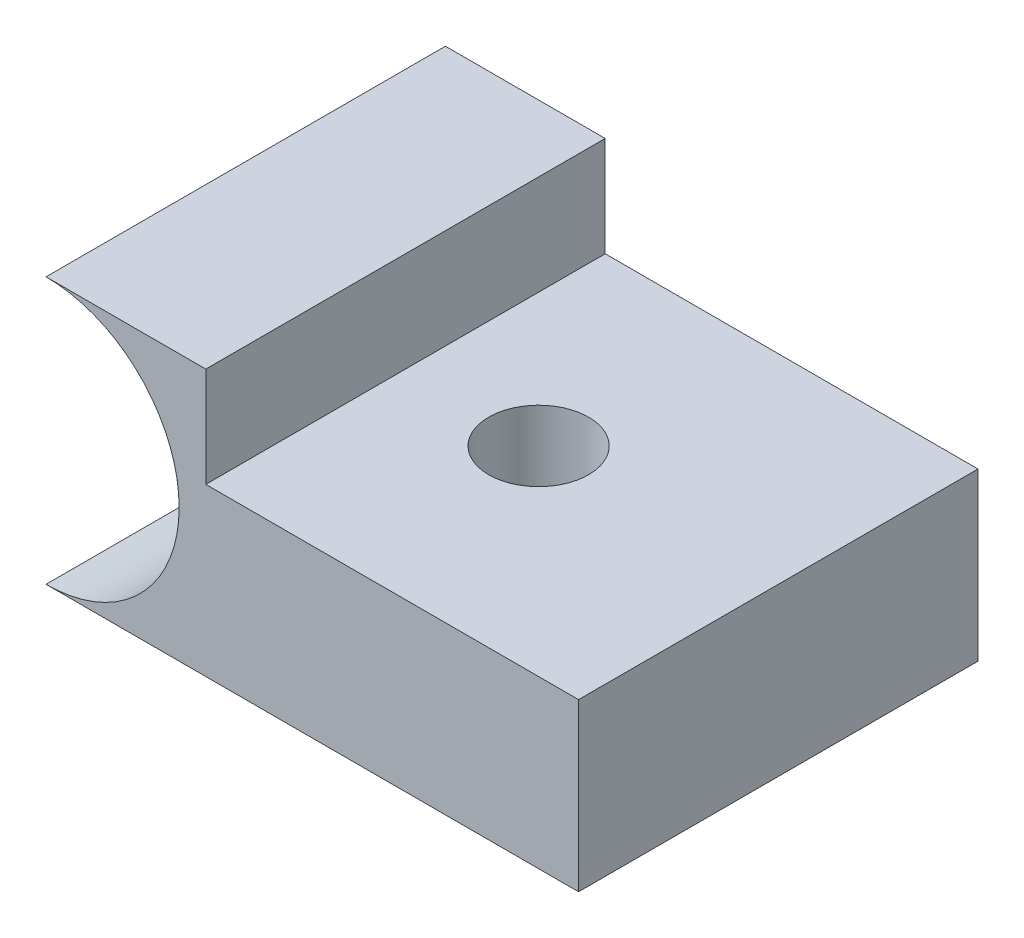
SolidWorks part; units mm, degrees
material "AISI Type A2 Tool Steel"
ref_plane "Front Plane" through (0, 0, 0) normal (0, 0, 1) x (1, 0, 0)
ref_plane "Top Plane" through (0, 0, 0) normal (0, 1, 0) x (1, 0, 0)
ref_plane "Right Plane" through (0, 0, 0) normal (1, 0, 0) x (0, 0, -1)
sketch "Sketch1" plane through (0, 0, 0) normal (0, 0, 1) x (1, 0, 0)
  line L1 (0, 0) -> (50.8, 0)
  line L3 (0, 25.4) -> (15.24, 25.4)
  line L4 (50.8, 0) -> (50.8, 15.875)
  line L6 (15.24, 25.4) -> (15.24, 15.875)
  line L7 (15.24, 15.875) -> (50.8, 15.875)
  arc A1 (0, 0) -> (0, 25.4) centre (0, 12.7) ccw
  dimension "D2" = 25.4
  dimension "D1" = 50.8
  dimension "D3" = 9.525
  dimension "D4" = 15.24
extrude "Boss-Extrude1" add sketch "Sketch1" along normal blind 38.1
sketch "Sketch2" plane through (0, 15.875, 0) normal (0, 1, 0) x (1, 0, 0)
  line L0 (0, -38.1) -> (0, 0) construction
  point P0 (27.94, -19.05)
  point P5 (0, -19.05)
  dimension "D1" = 27.94
hole_wizard "3/8 (0.375) Diameter Hole1" positions "Sketch2" profile "Sketch4" hole size "3/8" standard "ANSI Inch" end condition through all
sketch "Sketch4" plane through (27.94, 15.875, 19.05) normal (1, 0, 0) x (0, 0, 1)
  line L0 (0, 0) -> (0, 15.875)
  line L1 (0, 15.875) -> (4.7625, 15.875)
  line L2 (4.7625, 15.875) -> (4.7625, 0)
  line L5 (4.7625, 0) -> (0, 0)
  line L11 (0, -6.35) -> (0, 107.95) construction
  dimension "Thru Hole Dia." = 9.525
  dimension "Thru Hole Depth" = 15.875
